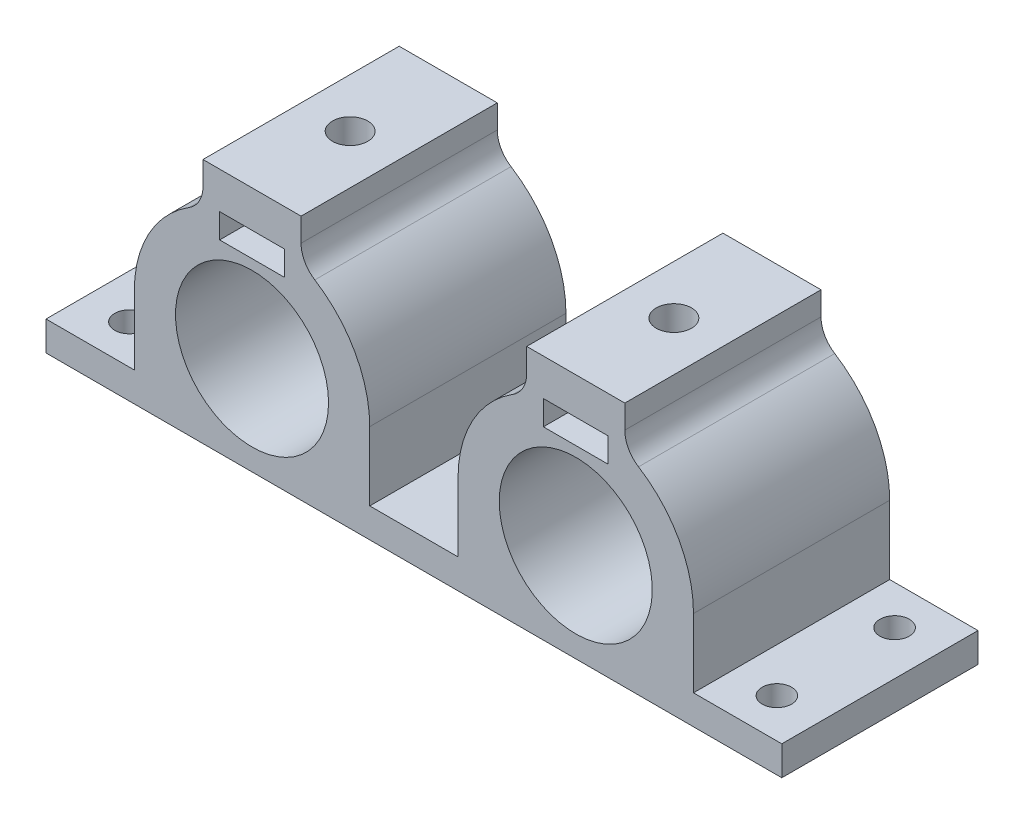
SolidWorks part; units mm, degrees
material "ABS"
ref_plane "Plano frontal" through (0, 0, 0) normal (0, 0, 1) x (1, 0, 0)
ref_plane "Plano superior" through (0, 0, 0) normal (0, 1, 0) x (1, 0, 0)
ref_plane "Plano direito" through (0, 0, 0) normal (1, 0, 0) x (0, 0, -1)
sketch "Esboço1" plane through (0, 0, 0) normal (0, 0, 1) x (1, 0, 0)
  line L0 (-12, 0) -> (-12, -7)
  line L2 (-21, -10) -> (-21, -7)
  line L3 (-21, -7) -> (-12, -7)
  line L4 (0, 11.0808) -> (0, -7.8) construction
  line L5 (21, -7) -> (12, -7)
  line L7 (12, 0) -> (12, -7)
  line L8 (0, 8.6919) -> (0, 15.0808) construction
  line L9 (5, 12.6886) -> (5, 15.0808)
  line L10 (-5, 12.6886) -> (-5, 15.0808)
  line L11 (-5, 8.6919) -> (-5, 15.0808) construction
  line L12 (5, 8.6919) -> (5, 15.0808) construction
  line L13 (5, 15.0808) -> (-5, 15.0808)
  line L14 (3.3, 11.3308) -> (-3.3, 11.3308)
  line L15 (3.3, 11.3308) -> (3.3, 8.8308)
  line L16 (3.3, 8.8308) -> (-3.3, 8.8308)
  line L17 (-3.3, 11.3308) -> (-3.3, 8.8308)
  line L18 (3.3, 11.3308) -> (-3.3, 8.8308) construction
  line L19 (3.3, 8.8308) -> (-3.3, 11.3308) construction
  line L20 (16.5, -8.8) -> (16.5, 23.7498) construction
  line L21 (29.7, 8.8308) -> (36.3, 11.3308) construction
  line L22 (29.7, 11.3308) -> (36.3, 8.8308) construction
  line L23 (33, 8.6919) -> (33, 15.0808) construction
  line L24 (33, 11.0808) -> (33, -7.8) construction
  line L25 (36.3, 11.3308) -> (36.3, 8.8308)
  line L26 (29.7, 8.8308) -> (36.3, 8.8308)
  line L27 (29.7, 11.3308) -> (29.7, 8.8308)
  line L28 (29.7, 11.3308) -> (36.3, 11.3308)
  line L29 (28, 15.0808) -> (38, 15.0808)
  line L30 (38, 12.6886) -> (38, 15.0808)
  line L31 (28, 12.6886) -> (28, 15.0808)
  line L32 (21, 0) -> (21, -7)
  line L35 (54, -7) -> (45, -7)
  line L36 (54, -10) -> (54, -7)
  line L37 (-21, -10) -> (54, -10)
  line L38 (45, 0) -> (45, -7)
  arc A0 (7.8, 0) -> (-7.8, 0) centre (0, 0) ccw
  arc A1 (12, 0) -> (6.4, 10.1509) centre (0, 0) ccw
  arc A2 (-7.8, 0) -> (7.8, 0) centre (0, 0) ccw
  arc A3 (-6.4, 10.1509) -> (-12, 0) centre (0, 0) ccw
  arc A4 (-6.4, 10.1509) -> (-5, 12.6886) centre (-8, 12.6886) ccw
  arc A5 (6.4, 10.1509) -> (5, 12.6886) centre (8, 12.6886) cw
  arc A6 (26.6, 10.1509) -> (28, 12.6886) centre (25, 12.6886) ccw
  arc A7 (39.4, 10.1509) -> (38, 12.6886) centre (41, 12.6886) cw
  arc A8 (39.4, 10.1509) -> (45, 0) centre (33, 0) cw
  arc A9 (40.8, 0) -> (25.2, 0) centre (33, 0) cw
  arc A10 (21, 0) -> (26.6, 10.1509) centre (33, 0) cw
  arc A11 (25.2, 0) -> (40.8, 0) centre (33, 0) cw
  point P14 (22, -5.2621)
  point P15 (0, -8.8)
  point P22 (0, 10.0808)
  point P58 (0, 0)
  point P62 (33, 10.0808)
  point P63 (33, -8.8)
  point P64 (-21.2009, -8.8)
  dimension "D2" = 12
  dimension "D3" = 7.8
  dimension "D9" = 3
  dimension "D4" = 5
  dimension "D5" = 75
  dimension "D6" = 5
  dimension "D7" = 4
  dimension "D8" = 5
  dimension "D10" = 33
  dimension "D11" = 3
  dimension "D12" = 10
extrude "Ressalto-extrusão1" add sketch "Esboço1" along normal blind 20
sketch "Esboço2" plane through (0, -7, 0) normal (0, 1, 0) x (1, 0, 0)
  line L0 (-12, -10) -> (-21, -10) construction
  line L1 (-12, -20) -> (-12, 0) construction
  line L2 (-21, -20) -> (-21, 0) construction
  line L3 (-16.5, -16) -> (-16.5, -4) construction
  line L4 (0, 0) -> (0, -28.0681) construction
  line L5 (16.5, 0) -> (16.5, -20) construction
  line L6 (21, 0) -> (12, 0) construction
  line L7 (33, 0) -> (33, -28.0681) construction
  line L8 (49.5, -16) -> (49.5, -4) construction
  line L9 (45, -10) -> (54, -10) construction
  line L10 (21, -20) -> (12, -20) construction
  circle A0 centre (-16.5, -4) radius 1.5
  circle A1 centre (-16.5, -16) radius 1.5
  circle A2 centre (49.5, -16) radius 1.5
  circle A3 centre (49.5, -4) radius 1.5
  circle A4 centre (16.5, -10) radius 1.5
  point P9 (-16.5, -10)
  point P30 (49.5, -10)
  dimension "D1" = 3
  dimension "D2" = 12
extrude "Corte-extrusão1" cut sketch "Esboço2" against normal blind 26 contours A1 | A0 | A4 | A3 | A2 region at (-16.5, -7, 4) region at (-16.5, -7, 16) region at (16.5, -7, 10)
sketch "Esboço4" plane through (0, 15.0808, 0) normal (0, 1, 0) x (1, 0, 0)
  line L0 (0, -20) -> (0, 0) construction
  line L1 (5, -20) -> (-5, -20) construction
  line L2 (5, 0) -> (-5, 0) construction
  line L3 (16.5, 0) -> (16.5, -20) construction
  line L4 (21, 0) -> (12, 0) construction
  line L5 (21, -20) -> (12, -20) construction
  line L6 (33, -20) -> (33, 0) construction
  circle A0 centre (0, -10) radius 1.8
  circle A1 centre (33, -10) radius 1.8
extrude "Corte-extrusão2" cut sketch "Esboço4" against normal blind 16
